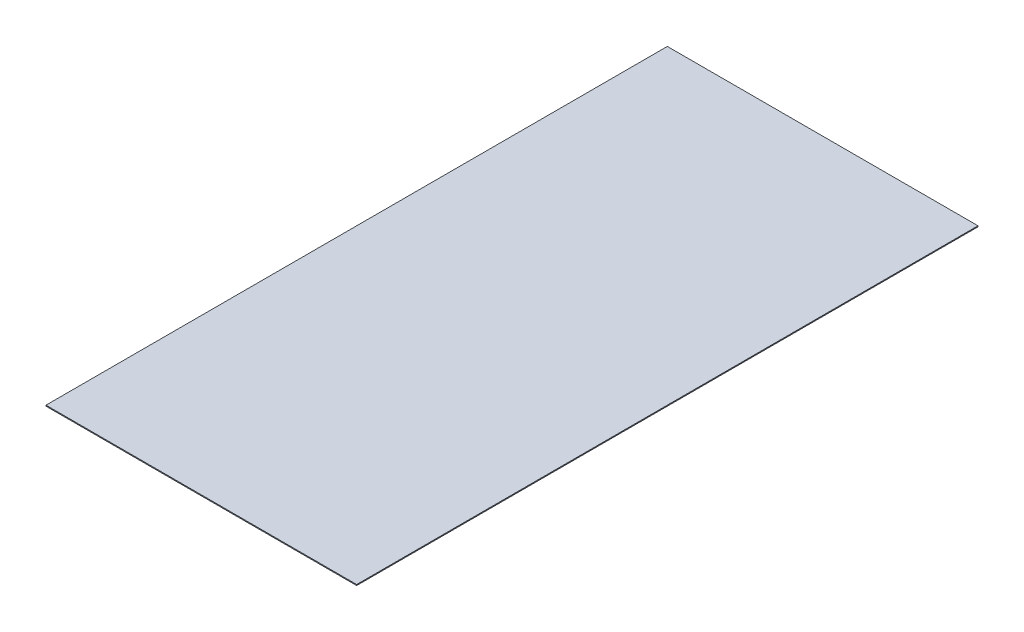
SolidWorks part; units mm, degrees
ref_plane "Front Plane" through (0, 0, 0) normal (0, 0, 1) x (1, 0, 0)
ref_plane "Top Plane" through (0, 0, 0) normal (0, 1, 0) x (1, 0, 0)
ref_plane "Right Plane" through (0, 0, 0) normal (1, 0, 0) x (0, 0, -1)
sketch "Sketch1" plane through (0, 0, 0) normal (0, 1, 0) x (1, 0, 0)
  line L1 (-500, -1000) -> (500, -1000)
  line L2 (-500, -1000) -> (-500, 1000)
  line L3 (-500, 1000) -> (500, 1000)
  line L4 (500, -1000) -> (500, 1000)
  line L5 (-500, -1000) -> (500, 1000) construction
  line L6 (-500, 1000) -> (500, -1000) construction
  point P0 (0, 0)
  dimension "D1" = 1000
  dimension "D2" = 2000
extrude "Boss-Extrude1" add sketch "Sketch1" along normal blind 3
equation "\"absorber_plate_width\" = 1000mm"
equation "\"absorber_plate_length\" = 2000mm"
equation "\"D2@Sketch1\"=\"absorber_plate_length\""
equation "\"D1@Sketch1\"=\"absorber_plate_width\""
equation "\"absorber_plate_thickness\" = 4mm"
equation "\"groove_depth\" = 10mm"
equation "\"frame_thickness\" = 60mm"
equation "\"bend_radius\"= 10mm"
equation "\"insulation_thickness\" = 50mm"
equation "\"glass_thickness\" = 3mm"
equation "\"D1@Boss-Extrude1\"=\"glass_thickness\""
